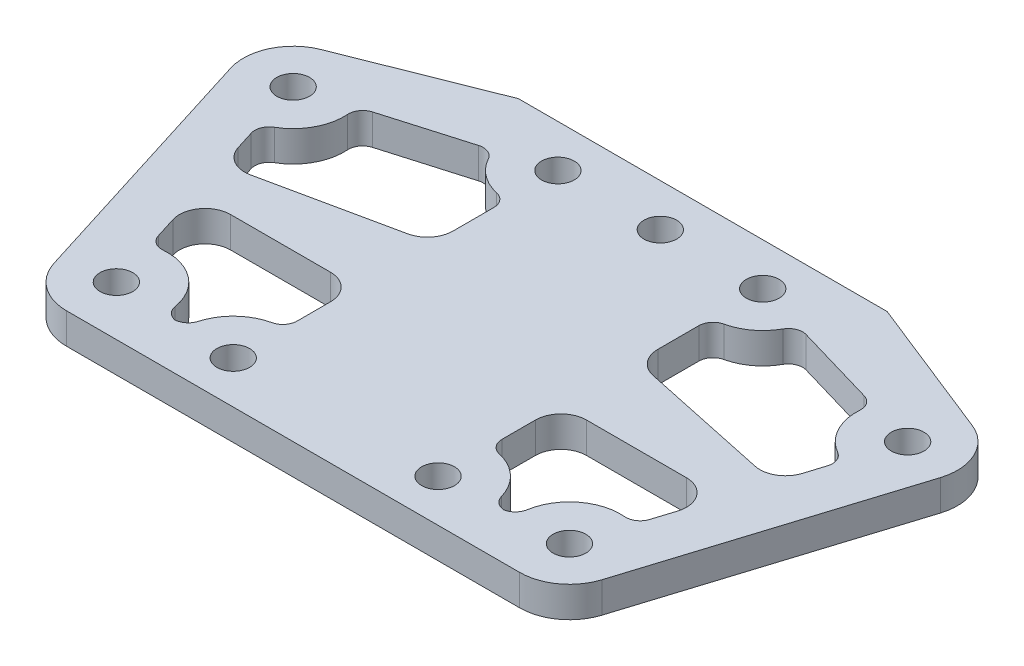
SolidWorks part; units mm, degrees
material "环氧树脂FR-4"
ref_plane "前视基准面" through (0, 0, 0) normal (0, 0, 1) x (1, 0, 0)
ref_plane "上视基准面" through (0, 0, 0) normal (0, 1, 0) x (1, 0, 0)
ref_plane "右视基准面" through (0, 0, 0) normal (1, 0, 0) x (0, 0, -1)
sketch "草图1" plane through (0, 0, 0) normal (0, 1, 0) x (1, 0, 0)
  line L0 (57.5, 0) -> (-57.5, 0) construction
  line L1 (0, 0) -> (0, 40) construction
  line L2 (42, 0) -> (-42, 0)
  line L3 (-42, 0) -> (-42, 40)
  line L4 (-42, 40) -> (0, 40)
  line L6 (42, 0) -> (42, 40)
  line L7 (42, 40) -> (0, 40)
  circle A0 centre (-22.12, 4.86) radius 1.6
  circle A1 centre (-30, 30) radius 1.6
  circle A2 centre (30, 30) radius 1.6
  circle A3 centre (22.12, 4.86) radius 1.6
  point P19 (0, 0)
  dimension "D5" = 30
  dimension "D6" = 3.2
  dimension "D4" = 22.12
  dimension "D1" = 25.14
  dimension "D2" = 30
  dimension "D3" = 115
  dimension "D7" = 0
  dimension "D8" = 40
  dimension "D9" = 42
extrude "凸台-拉伸1" add sketch "草图1" along normal blind 3
sketch "草图2" plane through (0, 3, 0) normal (0, 1, 0) x (1, 0, 0)
  line L0 (0, 0) -> (0, 40) construction
  line L1 (-42, 0) -> (42, 0) construction
  line L2 (42, 40) -> (-42, 40) construction
  line L4 (10, 4.15) -> (-10, 4.15) construction
  line L5 (10, 4.15) -> (10, 35.85) construction
  line L6 (10, 35.85) -> (-10, 35.85) construction
  line L7 (-10, 4.15) -> (-10, 35.85) construction
  line L8 (10, 4.15) -> (-10, 35.85) construction
  line L9 (10, 35.85) -> (-10, 4.15) construction
  circle A0 centre (-10, 35.85) radius 1.6
  circle A1 centre (10, 35.85) radius 1.6
  circle A2 centre (-10, 4.15) radius 1.6
  circle A3 centre (10, 4.15) radius 1.6
  circle A5 centre (0, 35.85) radius 1.6
  point P6 (0, 20)
  dimension "D4" = 3.2
  dimension "D1" = 20
  dimension "D2" = 31.7
  dimension "D3" = 20
extrude "切除-拉伸1" cut sketch "草图2" against normal through all
sketch "草图3" plane through (0, 3, 0) normal (0, 1, 0) x (1, 0, 0)
  line L0 (-26.7575, 3.4064) -> (-34.6375, 28.5464)
  line L1 (-42, 0) -> (42, 0) construction
  line L2 (-31.7953, 34.5163) -> (-18, 40)
  line L3 (42, 40) -> (-42, 40) construction
  line L4 (-42, 40) -> (-42, 0) construction
  line L5 (-18, 40) -> (-42, 40)
  line L6 (-42, 40) -> (-42, 0)
  line L7 (-42, 0) -> (-22.12, 0)
  line L8 (0, 0) -> (0, 40) construction
  line L9 (42, 0) -> (22.12, 0)
  line L10 (42, 40) -> (42, 0)
  line L11 (18, 40) -> (42, 40)
  line L12 (31.7953, 34.5163) -> (18, 40)
  line L13 (26.7575, 3.4064) -> (34.6375, 28.5464)
  circle A0 centre (-30, 30) radius 4.86
  circle A1 centre (-22.12, 4.86) radius 4.86
  circle A2 centre (22.12, 4.86) radius 4.86
  circle A3 centre (30, 30) radius 4.86
  line M9 (42, 40) -> (-42, 40)
  line M10 (-42, 40) -> (-42, 0)
  line M11 (-42, 0) -> (42, 0)
  line M12 (42, 0) -> (42, 40)
  dimension "D1" = 24
extrude "切除-拉伸2" cut sketch "草图3" against normal blind 10 contours A1 L0 A0 L2 M9 M10 M11 | L12 A3 L13 A2 M11 M12 M9 region at (-35.4168, 3, -19.1851) region at (35.4168, 3, -19.1851)
sketch "草图4" plane through (0, 3, 0) normal (0, 1, 0) x (1, 0, 0)
  line L0 (-30, 30) -> (-10, 35.85)
  line L1 (-30, 30) -> (-22.12, 4.86)
  line L2 (-22.12, 4.86) -> (-10, 4.15)
  line L3 (-10, 4.15) -> (-10, 35.85)
  line L4 (-26.8656, 20) -> (-10, 23.5849)
  line L5 (-25.6588, 16.15) -> (-10, 16.15)
  circle A0 centre (-30, 30) radius 5
  circle A1 centre (-22.12, 4.86) radius 5
  circle A2 centre (-10, 4.15) radius 5
  circle A3 centre (-10, 35.85) radius 5
  dimension "D1" = 10
  dimension "D2" = 12
  dimension "D3" = 10
  dimension "D4" = 12
extrude "切除-拉伸3" cut sketch "草图4" against normal blind 10 contours A3 L0 A0 L1 L4 L3 | A2 L3 L5 L1 A1 L2 region at (-18.788, 3, -26.9411) region at (-16.9666, 3, -11.9719)
fillet "圆角1" radius 2.5 4 edges at (-10, 1.5, -16.15) (-25.6588, 1.5, -16.15) (-10, 1.5, -23.5849) (-26.8656, 1.5, -20)
fillet "圆角2" radius 1.4 8 edges at (-23.6155, 1.5, -9.6311) (-10, 1.5, -9.15) (-10, 1.5, -30.85) (-14.7989, 1.5, -34.4463) (-25.2011, 1.5, -31.4037) (-28.5045, 1.5, -25.2289) (-14.9914, 1.5, -4.4424) (-17.1286, 1.5, -4.5676)
mirror "镜向1" about plane through (0, 0, 0) normal (1, 0, 0) of "圆角2", "圆角1", "切除-拉伸3"
